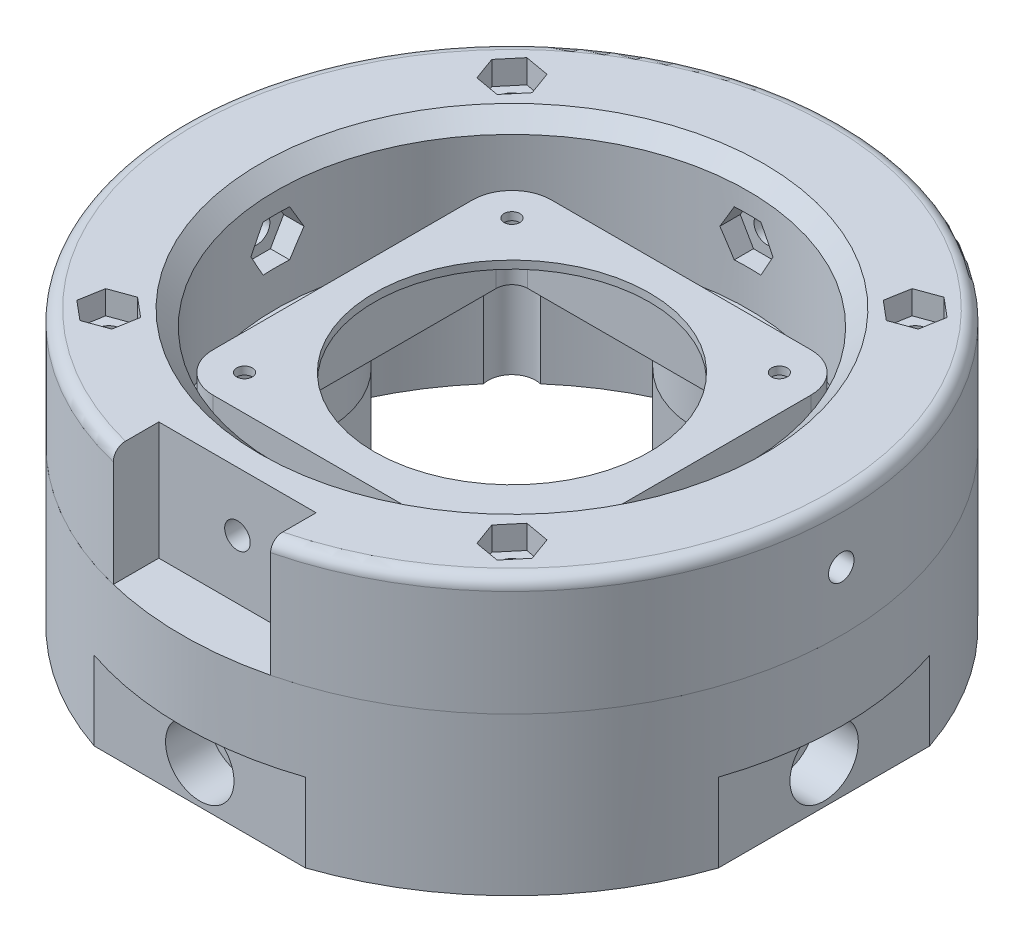
SolidWorks part; units mm, degrees
ref_plane "Front" through (0, 0, 0) normal (0, 0, 1) x (1, 0, 0)
ref_plane "Top" through (0, 0, 0) normal (0, 1, 0) x (1, 0, 0)
ref_plane "Right" through (0, 0, 0) normal (1, 0, 0) x (0, 0, -1)
sketch "Sketch1" plane through (0, 0, 0) normal (0, 1, 0) x (1, 0, 0)
  circle A0 centre (0, 0) radius 41.9
  dimension "D1" = 83.8
extrude "Top-Part" add sketch "Sketch1" along normal blind 15
sketch "Sketch2" plane through (0, 15, 0) normal (0, 1, 0) x (1, 0, 0)
  circle A0 centre (0, 0) radius 30
  dimension "D1" = 60
extrude "Cut-Extrude1" cut sketch "Sketch2" against normal blind 20
fillet "Fillet1" radius 1.5 1 edges at (0, 15, 41.9)
chamfer "Chamfer1" distance 2 angle 45 1 edges at (0, 15, 30)
sketch "Sketch8" plane through (0, 15, 0) normal (0, 1, 0) x (1, 0, 0)
  line L0 (0, 0) -> (0, 52.711) construction
  line L1 (25.0832, 22.5168) -> (28.0563, 23.5989)
  line L8 (0, 0) -> (-43.3951, 43.3951) construction
  line L9 (-25.6326, 25.6326) -> (-25.6326, 34.5059) construction
  line L10 (-22.5168, 25.0832) -> (-23.5989, 28.0563)
  line L11 (-23.5989, 28.0563) -> (-26.7147, 28.6057)
  line L12 (-26.7147, 28.6057) -> (-28.7485, 26.182)
  line L13 (-28.7485, 26.182) -> (-27.6663, 23.2089)
  line L14 (-27.6663, 23.2089) -> (-24.5505, 22.6595)
  line L15 (-24.5505, 22.6595) -> (-22.5168, 25.0832)
  line L16 (28.0563, 23.5989) -> (28.6057, 26.7147)
  line L17 (28.6057, 26.7147) -> (26.182, 28.7485)
  line L18 (26.182, 28.7485) -> (23.2089, 27.6663)
  line L19 (23.2089, 27.6663) -> (22.6595, 24.5505)
  line L20 (22.6595, 24.5505) -> (25.0832, 22.5168)
  line L21 (0, 0) -> (43.3951, 43.3951) construction
  line L23 (22.5168, -25.0832) -> (23.5989, -28.0563)
  line L24 (23.5989, -28.0563) -> (26.7147, -28.6057)
  line L25 (26.7147, -28.6057) -> (28.7485, -26.182)
  line L26 (28.7485, -26.182) -> (27.6663, -23.2089)
  line L27 (27.6663, -23.2089) -> (24.5505, -22.6595)
  line L28 (24.5505, -22.6595) -> (22.5168, -25.0832)
  line L29 (0, 0) -> (43.3951, -43.3951) construction
  line L31 (-25.0832, -22.5168) -> (-28.0563, -23.5989)
  line L32 (-28.0563, -23.5989) -> (-28.6057, -26.7147)
  line L33 (-28.6057, -26.7147) -> (-26.182, -28.7485)
  line L34 (-26.182, -28.7485) -> (-23.2089, -27.6663)
  line L35 (-23.2089, -27.6663) -> (-22.6595, -24.5505)
  line L36 (-22.6595, -24.5505) -> (-25.0832, -22.5168)
  line L37 (0, 0) -> (-43.3951, -43.3951) construction
  line L39 (-25.6326, 25.6326) -> (-27.9138, 12.6954) construction
  circle A0 centre (0, 0) radius 36.25 construction
  circle A1 centre (25.6326, 25.6326) radius 2.74 construction
  circle A2 centre (-25.6326, 25.6326) radius 2.74 construction
  circle A3 centre (25.6326, -25.6326) radius 2.74 construction
  circle A4 centre (-25.6326, -25.6326) radius 2.74 construction
  circle A5 centre (-25.6326, 25.6326) radius 1.625
  circle A6 centre (25.6326, 25.6326) radius 1.625
  circle A7 centre (25.6326, -25.6326) radius 1.625
  circle A8 centre (-25.6326, -25.6326) radius 1.625
  point P8 (25.6326, 25.6326)
  point P10 (28.331, 25.1568)
  point P18 (-25.6326, 25.6326)
  point P20 (-25.1568, 28.331)
  point P36 (25.6326, -25.6326)
  point P38 (25.1568, -28.331)
  point P50 (-25.6326, -25.6326)
  point P52 (-28.331, -25.1568)
  point P63 (0, 0)
  point P69 (-27.8231, 23.2366)
  dimension "D1" = 72.5
  dimension "D5" = 3.25
  dimension "D2" = 4
  dimension "D3" = 45
  dimension "D4" = 10
  dimension "D6" = 5.75
extrude "Cut-Extrude8" cut sketch "Sketch8<7>" against normal blind 3
sketch "Sketch8<7>" plane through (0, 15, 0) normal (0, 1, 0) x (1, 0, 0) same geometry as "Sketch8"
extrude "Cut-Extrude7" cut sketch "Sketch8" against normal through all contours A5 | A6 | A7 | A8
sketch "Sketch13" plane through (0, 0, 0) normal (0, -1, 0) x (1, 0, 0)
  line L0 (0, 0) -> (0, 66.0162) construction
  line L1 (-10, 35.5191) -> (-10, 40.6892)
  line L2 (10, 35.5191) -> (10, 40.6892)
  line L3 (-10, 40.6892) -> (10, 35.5191) construction
  line L4 (10, 40.6892) -> (-10, 35.5191) construction
  circle A0 centre (0, 0) radius 41.9 construction
  arc A1 (10, 40.6892) -> (-10, 40.6892) centre (0, 0) ccw
  arc A2 (10, 35.5191) -> (-10, 35.5191) centre (0, 0) ccw
  point P6 (0, 38.1042)
  point P10 (0, 36.9)
  point P12 (0, 41.9)
  dimension "D1" = 10
  dimension "D3" = 5
extrude "Cut-Extrude11" cut sketch "Sketch13" against normal through all
ref_plane "Plane2" through (0, 0, 41.9) normal (0, 0, 1) x (1, 0, 0)
ref_plane "Plane3" through (0, 0, 32.4) normal (0, 0, 1) x (1, 0, 0)
sketch "Sketch15" plane through (0, 0, 32.4) normal (0, 0, 1) x (1, 0, 0)
  line L0 (0, -23.0183) -> (0, 33.1182) construction
  circle A1 centre (0, 7.5) radius 1.625
  point P11 (0, 7.5)
  dimension "D3" = 3.25
  dimension "D1" = 7.5
extrude "Cut-Extrude14" cut sketch "Sketch15" against normal blind 10 and the other way blind 10
sketch "Sketch16" plane through (0, 0, 32.4) normal (0, 0, 1) x (1, 0, 0)
  line L0 (0, 0) -> (0, 26.985) construction
  line L2 (3.3775, 7.5) -> (1.6887, 10.425)
  line L3 (1.6887, 10.425) -> (-1.6887, 10.425)
  line L4 (-1.6887, 10.425) -> (-3.3775, 7.5)
  line L5 (-3.3775, 7.5) -> (-1.6887, 4.575)
  line L6 (-1.6887, 4.575) -> (1.6887, 4.575)
  line L7 (1.6887, 4.575) -> (3.3775, 7.5)
  circle A0 centre (0, 7.5) radius 2.925 construction
  point P4 (0, 4.575)
  point P13 (0, 10.425)
  dimension "D1" = 5.85
  dimension "D2" = 7.5
extrude "Cut-Extrude15" cut sketch "Sketch16" against normal blind 10
pattern_circular "CirPattern1" count 4 over 360 about axis through (0, 0, 0) along (0, 1, 0) of "Cut-Extrude14"
pattern_circular "CirPattern2" count 4 every 90 about axis through (0, 0, 0) along (0, 1, 0) of "Cut-Extrude15"
sketch "Sketch3" plane through (0, 0, 0) normal (0, -1, 0) x (1, 0, 0)
  circle A0 centre (0, 0) radius 41.9
  dimension "D1" = 83.8
extrude "Bottom-Part" add sketch "Sketch3" along normal blind 20 separate body
ref_plane "Plane1" through (0, -1.5, 0) normal (0, 1, 0) x (1, 0, 0)
sketch "Sketch6" plane through (0, -1.5, 0) normal (0, 1, 0) x (1, 0, 0)
  line L0 (0, 0) -> (-97.4577, 0) construction
  line L5 (-37.9, 0) -> (-41.9, 0) construction
  circle A0 centre (0, 0) radius 37.9
  circle A1 centre (0, 0) radius 41.9 construction
  circle A2 centre (0, 0) radius 41.9 construction
  point P6 (-37.9, 0)
  point P9 (-41.9, 0)
  dimension "D1" = 4
extrude "Cut-Extrude3" cut sketch "Sketch6" against normal through all
sketch "ｽｹｯﾁ1" plane through (0, 0, 0) normal (0, 1, 0) x (1, 0, 0)
  line L3 (21.5, -21.5) -> (-21.5, -21.5)
  line L4 (21.5, -21.5) -> (21.5, 21.5)
  line L5 (21.5, 21.5) -> (-21.5, 21.5)
  line L6 (-21.5, -21.5) -> (-21.5, 21.5)
  line L7 (21.5, -21.5) -> (-21.5, 21.5) construction
  line L8 (21.5, 21.5) -> (-21.5, -21.5) construction
  point P2 (0, 0)
  dimension "D1" = 43
extrude "ﾎﾞｽ - 押し出し1" add sketch "ｽｹｯﾁ1" along normal blind 8
fillet "ﾌｨﾚｯﾄ1" radius 5 4 edges at (21.5, 4, -21.5) (-21.5, 4, -21.5) (-21.5, 4, 21.5) (21.5, 4, 21.5)
sketch "Sketch7" plane through (0, -1.5, 0) normal (0, 1, 0) x (1, 0, 0)
  circle A0 centre (0, 0) radius 17.5
  circle A1 centre (17, -17) radius 1
  circle A2 centre (-17, -17) radius 1
  circle A3 centre (-17, 17) radius 1
  circle A4 centre (17, 17) radius 1
  dimension "D1" = 35
  dimension "D2" = 2
extrude "Cut-Extrude4" cut sketch "Sketch7" against normal through all and the other way through all
sketch "Sketch12" plane through (0, -1.5, 0) normal (0, -1, 0) x (1, 0, 0)
  line L1 (19.75, -19.75) -> (-19.75, -19.75)
  line L2 (19.75, -19.75) -> (19.75, 19.75)
  line L3 (19.75, 19.75) -> (-19.75, 19.75)
  line L4 (-19.75, -19.75) -> (-19.75, 19.75)
  line L5 (19.75, -19.75) -> (-19.75, 19.75) construction
  line L6 (19.75, 19.75) -> (-19.75, -19.75) construction
  point P0 (0, 0)
  dimension "D1" = 39.5
extrude "Cut-Extrude10" cut sketch "Sketch12" against normal blind 8.5
fillet "Fillet3" radius 2 4 edges at (-19.75, 2.75, -19.75) (-19.75, 2.75, 19.75) (19.75, 2.75, -19.75) (19.75, 2.75, 19.75)
sketch "Sketch17" plane through (0, -1.5, 0) normal (0, -1, 0) x (1, 0, 0)
  circle A0 centre (25.6326, -25.6326) radius 1.625 construction
  circle A1 centre (-25.6326, -25.6326) radius 1.625 construction
  circle A2 centre (25.6326, 25.6326) radius 1.625 construction
  circle A3 centre (-25.6326, 25.6326) radius 1.625 construction
  circle A4 centre (25.6326, -25.6326) radius 1.625
  circle A5 centre (-25.6326, -25.6326) radius 1.625
  circle A6 centre (25.6326, 25.6326) radius 1.625
  circle A7 centre (-25.6326, 25.6326) radius 1.625
extrude "Cut-Extrude16" cut sketch "Sketch17" against normal through all
sketch "Sketch18" plane through (0, -1.5, 0) normal (0, -1, 0) x (1, 0, 0)
  circle A0 centre (-25.6326, 25.6326) radius 3
  circle A1 centre (25.6326, 25.6326) radius 3
  circle A2 centre (25.6326, -25.6326) radius 3
  circle A3 centre (-25.6326, -25.6326) radius 3
  dimension "D1" = 6
extrude "Cut-Extrude17" cut sketch "Sketch18" along normal through all
sketch "Sketch19" plane through (0, -1.5, 0) normal (0, -1, 0) x (1, 0, 0)
  arc A1 (35.4434, 13.423) -> (35.4434, -13.423) centre (37, 0) ccw
  arc A2 (35.4434, -13.423) -> (35.4434, 13.423) centre (0, 0) ccw
  arc A14 (-13.423, 35.4434) -> (13.423, 35.4434) centre (0, 37) ccw
  arc A15 (24.9276, 28.5486) -> (-24.9276, 28.5486) centre (0, 0) ccw construction
  arc A16 (13.423, 35.4434) -> (-13.423, 35.4434) centre (0, 0) ccw
  arc A17 (13.423, -35.4434) -> (-13.423, -35.4434) centre (0, -37) ccw
  arc A18 (-13.423, -35.4434) -> (13.423, -35.4434) centre (0, 0) ccw
  arc A19 (-35.4434, -13.423) -> (-35.4434, 13.423) centre (-37, 0) ccw
  arc A20 (-35.4434, 13.423) -> (-35.4434, -13.423) centre (0, 0) ccw
  dimension "D1" = 37
  dimension "D2" = 4
extrude "Boss-Extrude1" add sketch "Sketch19" along normal blind 8.5
sketch "Sketch23" plane through (0, -10, 0) normal (0, -1, 0) x (1, 0, 0)
  line L1 (9.7077, -27.6) -> (-9.7077, -27.6)
  line L2 (27.6, -9.7077) -> (27.6, 9.7077)
  line L3 (9.7077, 27.6) -> (-9.7077, 27.6)
  line L4 (-27.6, -9.7077) -> (-27.6, 9.7077)
  line L5 (27.6, -27.6) -> (-27.6, 27.6) construction
  line L6 (27.6, 27.6) -> (-27.6, -27.6) construction
  arc A0 (-13.423, -35.4434) -> (13.423, -35.4434) centre (0, 0) ccw construction
  arc A1 (-28.5486, 24.9276) -> (-28.5486, -24.9276) centre (0, 0) ccw construction
  arc A2 (13.423, 35.4434) -> (-13.423, 35.4434) centre (0, 0) ccw construction
  arc A3 (35.4434, -13.423) -> (35.4434, 13.423) centre (0, 0) ccw construction
  arc A4 (35.4434, 13.423) -> (35.4434, -13.423) centre (37, 0) ccw construction
  arc A5 (13.423, -35.4434) -> (-13.423, -35.4434) centre (0, -37) ccw construction
  arc A6 (-35.4434, -13.423) -> (-35.4434, 13.423) centre (-37, 0) ccw construction
  arc A7 (-13.423, 35.4434) -> (13.423, 35.4434) centre (0, 37) ccw construction
  arc A8 (-13.423, -35.4434) -> (13.423, -35.4434) centre (0, 0) ccw
  arc A9 (-35.4434, 13.423) -> (-35.4434, -13.423) centre (0, 0) ccw
  arc A10 (13.423, 35.4434) -> (-13.423, 35.4434) centre (0, 0) ccw
  arc A11 (35.4434, -13.423) -> (35.4434, 13.423) centre (0, 0) ccw
  arc A12 (35.4434, 13.423) -> (27.6, 9.7077) centre (37, 0) ccw
  arc A13 (13.423, -35.4434) -> (9.7077, -27.6) centre (0, -37) ccw
  arc A14 (-35.4434, -13.423) -> (-27.6, -9.7077) centre (-37, 0) ccw
  arc A15 (-13.423, 35.4434) -> (-9.7077, 27.6) centre (0, 37) ccw
  arc A16 (27.6, -9.7077) -> (35.4434, -13.423) centre (37, 0) ccw
  arc A17 (9.7077, 27.6) -> (13.423, 35.4434) centre (0, 37) ccw
  arc A18 (-27.6, 9.7077) -> (-35.4434, 13.423) centre (-37, 0) ccw
  arc A19 (-9.7077, -27.6) -> (-13.423, -35.4434) centre (0, -37) ccw
  point P0 (0, 0)
  dimension "D1" = 55.2
  dimension "D2" = 55.2
extrude "Boss-Extrude2" add sketch "Sketch23" along normal blind 10
sketch "Sketch27" plane through (0, -20, 0) normal (0, -1, 0) x (1, 0, 0)
  line L0 (39.6917, 13.423) -> (39.6917, -13.423)
  line L1 (-13.423, 39.6917) -> (13.423, 39.6917)
  line L2 (13.423, -39.6917) -> (-13.423, -39.6917)
  line L3 (-39.6917, -13.423) -> (-39.6917, 13.423)
  circle A0 centre (0, 0) radius 41.9 construction
  arc A1 (13.423, 39.6917) -> (-13.423, 39.6917) centre (0, 0) ccw
  arc A2 (39.6917, -13.423) -> (39.6917, 13.423) centre (0, 0) ccw
  arc A3 (-13.423, -39.6917) -> (13.423, -39.6917) centre (0, 0) ccw
  arc A4 (-39.6917, 13.423) -> (-39.6917, -13.423) centre (0, 0) ccw
  dimension "D1" = 4
extrude "Cut-Extrude18" cut sketch "Sketch27" against normal blind 10
sketch "Sketch28" plane through (0, 0, 39.6917) normal (0, 0, 1) x (1, 0, 0)
  line L0 (-13.423, -20) -> (13.423, -20) construction
  circle A0 centre (0, -15) radius 2.75
  dimension "D1" = 5.5
  dimension "D2" = 5
extrude "Cut-Extrude19" cut sketch "Sketch28" against normal blind 13
sketch "Sketch29" plane through (0, 0, 39.6917) normal (0, 0, 1) x (1, 0, 0)
  circle A0 centre (0, -15) radius 4.35
extrude "Cut-Extrude20" cut sketch "Sketch29" against normal blind 5.5
pattern_circular "CirPattern3" count 4 over 360 about axis through (0, -20, 0) along (0, -1, 0) of "Cut-Extrude19", "Cut-Extrude20"
sketch "Sketch30" plane through (0, 15, 0) normal (0, 1, 0) x (1, 0, 0)
  line L0 (-10, -39.1428) -> (-10, -35.5191) construction
  line L1 (-10, -44.1135) -> (10, -44.1135)
  line L2 (-10, -44.1135) -> (-10, -34.9)
  line L3 (-10, -34.9) -> (10, -34.9)
  line L4 (10, -44.1135) -> (10, -34.9)
  dimension "D1" = 34.9
extrude "Cut-Extrude21" cut sketch "Sketch30" against normal up to surface (15 mm away) up to face at (-25.6326, 0, -27.2576)
